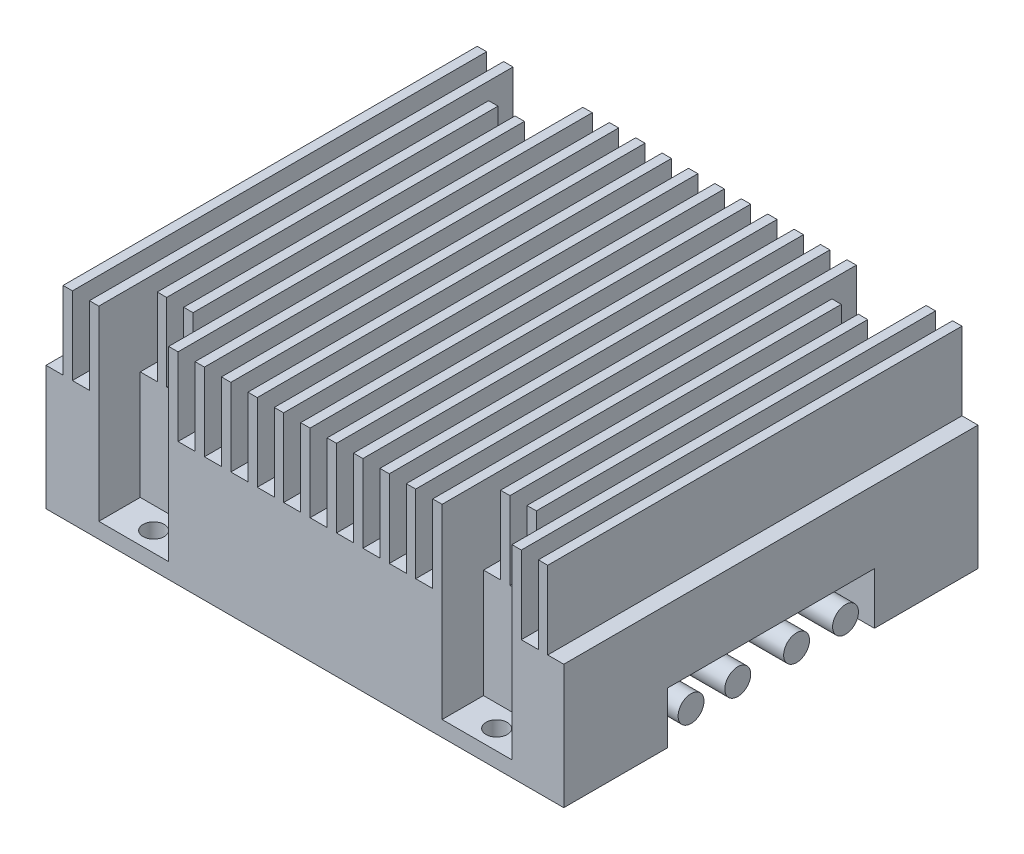
SolidWorks part; units mm, degrees
ref_plane "前视基准面" through (0, 0, 0) normal (0, 0, 1) x (1, 0, 0)
ref_plane "上视基准面" through (0, 0, 0) normal (0, 1, 0) x (1, 0, 0)
ref_plane "右视基准面" through (0, 0, 0) normal (1, 0, 0) x (0, 0, -1)
sketch "草图1" plane through (0, 0, 0) normal (0, 1, 0) x (1, 0, 0)
  line L1 (-50, 40) -> (50, 40)
  line L2 (-50, 40) -> (-50, -40)
  line L3 (-50, -40) -> (50, -40)
  line L4 (50, 40) -> (50, -40)
  line L5 (-50, 40) -> (50, -40) construction
  line L6 (-50, -40) -> (50, 40) construction
  point P0 (0, 0)
  dimension "D1" = 100
  dimension "D2" = 80
extrude "凸台-拉伸1" add sketch "草图1" along normal blind 39
sketch "草图2" plane through (0, 39, 0) normal (0, 1, 0) x (1, 0, 0)
  line L0 (-50, -40) -> (50, -40) construction
  line L1 (-50, 40) -> (-46.7121, 40)
  line L2 (-50, 40) -> (-50, -40)
  line L3 (-50, -40) -> (-46.7121, -40)
  line L4 (-46.7121, 40) -> (-46.7121, -40)
  line L5 (-44.9, 40) -> (-44.9, -40)
  line L6 (-44.9, 40) -> (-41.6121, 40)
  line L7 (-41.6121, 40) -> (-41.6121, -40)
  line L8 (-44.9, -40) -> (-41.6121, -40)
  line L9 (-39.8, 40) -> (-39.8, -40)
  line L10 (-39.8, 40) -> (-36.5121, 40)
  line L11 (-36.5121, 40) -> (-36.5121, -40)
  line L12 (-39.8, -40) -> (-36.5121, -40)
  line L13 (-34.7, 40) -> (-34.7, -40)
  line L14 (-34.7, 40) -> (-31.4121, 40)
  line L15 (-31.4121, 40) -> (-31.4121, -40)
  line L16 (-34.7, -40) -> (-31.4121, -40)
  line L17 (-29.6, 40) -> (-29.6, -40)
  line L18 (-29.6, 40) -> (-26.3121, 40)
  line L19 (-26.3121, 40) -> (-26.3121, -40)
  line L20 (-29.6, -40) -> (-26.3121, -40)
  line L21 (-24.5, 40) -> (-24.5, -40)
  line L22 (-24.5, 40) -> (-21.2121, 40)
  line L23 (-21.2121, 40) -> (-21.2121, -40)
  line L24 (-24.5, -40) -> (-21.2121, -40)
  line L25 (-19.4, 40) -> (-19.4, -40)
  line L26 (-19.4, 40) -> (-16.1121, 40)
  line L27 (-16.1121, 40) -> (-16.1121, -40)
  line L28 (-19.4, -40) -> (-16.1121, -40)
  line L29 (-14.3, 40) -> (-14.3, -40)
  line L30 (-14.3, 40) -> (-11.0121, 40)
  line L31 (-11.0121, 40) -> (-11.0121, -40)
  line L32 (-14.3, -40) -> (-11.0121, -40)
  line L33 (-9.2, 40) -> (-9.2, -40)
  line L34 (-9.2, 40) -> (-5.9121, 40)
  line L35 (-5.9121, 40) -> (-5.9121, -40)
  line L36 (-9.2, -40) -> (-5.9121, -40)
  line L37 (-4.1, 40) -> (-4.1, -40)
  line L38 (-4.1, 40) -> (-0.8121, 40)
  line L39 (-0.8121, 40) -> (-0.8121, -40)
  line L40 (-4.1, -40) -> (-0.8121, -40)
  line L41 (1, 40) -> (1, -40)
  line L42 (1, 40) -> (4.2879, 40)
  line L43 (4.2879, 40) -> (4.2879, -40)
  line L44 (1, -40) -> (4.2879, -40)
  line L45 (6.1, 40) -> (6.1, -40)
  line L46 (6.1, 40) -> (9.3879, 40)
  line L47 (9.3879, 40) -> (9.3879, -40)
  line L48 (6.1, -40) -> (9.3879, -40)
  line L49 (11.2, 40) -> (11.2, -40)
  line L50 (11.2, 40) -> (14.4879, 40)
  line L51 (14.4879, 40) -> (14.4879, -40)
  line L52 (11.2, -40) -> (14.4879, -40)
  line L53 (16.3, 40) -> (16.3, -40)
  line L54 (16.3, 40) -> (19.5879, 40)
  line L55 (19.5879, 40) -> (19.5879, -40)
  line L56 (16.3, -40) -> (19.5879, -40)
  line L57 (21.4, 40) -> (21.4, -40)
  line L58 (21.4, 40) -> (24.6879, 40)
  line L59 (24.6879, 40) -> (24.6879, -40)
  line L60 (21.4, -40) -> (24.6879, -40)
  line L61 (26.5, 40) -> (26.5, -40)
  line L62 (26.5, 40) -> (29.7879, 40)
  line L63 (29.7879, 40) -> (29.7879, -40)
  line L64 (26.5, -40) -> (29.7879, -40)
  line L65 (31.6, 40) -> (31.6, -40)
  line L66 (31.6, 40) -> (34.8879, 40)
  line L67 (34.8879, 40) -> (34.8879, -40)
  line L68 (31.6, -40) -> (34.8879, -40)
  line L69 (36.7, 40) -> (36.7, -40)
  line L70 (36.7, 40) -> (39.9879, 40)
  line L71 (39.9879, 40) -> (39.9879, -40)
  line L72 (36.7, -40) -> (39.9879, -40)
  line L73 (41.8, 40) -> (41.8, -40)
  line L74 (41.8, 40) -> (45.0879, 40)
  line L75 (45.0879, 40) -> (45.0879, -40)
  line L76 (41.8, -40) -> (45.0879, -40)
  line L77 (46.9, 40) -> (46.9, -40)
  line L78 (46.9, 40) -> (50.1879, 40)
  line L79 (50.1879, 40) -> (50.1879, -40)
  line L80 (46.9, -40) -> (50.1879, -40)
  dimension "D1" = 20
extrude "切除-拉伸1" cut sketch "草图2" against normal blind 15
sketch "草图3" plane through (0, 24, 0) normal (0, 1, 0) x (1, 0, 0)
  line L0 (-26.3121, -40) -> (-26.3121, 40) construction
  line L1 (-39.8, 40) -> (-26.3121, 40)
  line L2 (-39.8, 40) -> (-39.8, 32)
  line L3 (-39.8, 32) -> (-26.3121, 32)
  line L4 (-26.3121, 40) -> (-26.3121, 32)
  dimension "D1" = 8
extrude "切除-拉伸2" cut sketch "草图3" against normal blind 21
extrude "切除-拉伸3" cut sketch "草图3<2>" along normal blind 15
sketch "草图3<2>" plane through (0, 24, 0) normal (0, 1, 0) x (1, 0, 0) same geometry as "草图3"
sketch "草图4" plane through (0, 24, 0) normal (0, 1, 0) x (1, 0, 0)
  line L0 (26.5, 40) -> (26.5, -40) construction
  line L1 (39.9879, 40) -> (26.5, 40)
  line L2 (39.9879, 40) -> (39.9879, 32)
  line L3 (39.9879, 32) -> (26.5, 32)
  line L4 (26.5, 40) -> (26.5, 32)
  dimension "D1" = 8
extrude "切除-拉伸4" cut sketch "草图4" against normal blind 21
extrude "切除-拉伸5" cut sketch "草图4<3>" along normal blind 15
sketch "草图4<3>" plane through (0, 24, 0) normal (0, 1, 0) x (1, 0, 0) same geometry as "草图4"
sketch "草图5" plane through (0, 24, 0) normal (0, 1, 0) x (1, 0, 0)
  line L0 (-26.3121, -40) -> (-26.3121, 32) construction
  line L1 (-39.8, -40) -> (-26.3121, -40)
  line L2 (-39.8, -40) -> (-39.8, -32)
  line L3 (-39.8, -32) -> (-26.3121, -32)
  line L4 (-26.3121, -40) -> (-26.3121, -32)
  dimension "D1" = 8
extrude "切除-拉伸6" cut sketch "草图5" against normal blind 21
extrude "切除-拉伸7" cut sketch "草图5<2>" along normal blind 15
sketch "草图5<2>" plane through (0, 24, 0) normal (0, 1, 0) x (1, 0, 0) same geometry as "草图5"
sketch "草图6" plane through (0, 39, 0) normal (0, 1, 0) x (1, 0, 0)
  line L0 (26.5, 40) -> (26.5, -40) construction
  line L1 (39.9879, -40) -> (26.5, -40)
  line L2 (39.9879, -40) -> (39.9879, -32)
  line L3 (39.9879, -32) -> (26.5, -32)
  line L4 (26.5, -40) -> (26.5, -32)
  dimension "D1" = 8
extrude "切除-拉伸8" cut sketch "草图6" against normal blind 21
extrude "切除-拉伸9" cut sketch "草图6<2>" against normal blind 36
sketch "草图6<2>" plane through (0, 39, 0) normal (0, 1, 0) x (1, 0, 0) same geometry as "草图6"
sketch "草图7" plane through (0, 3, 0) normal (0, 1, 0) x (1, 0, 0)
  circle A0 centre (-33.3959, 36.0216) radius 2.05
  dimension "D1" = 4.1
extrude "切除-拉伸10" cut sketch "草图7" against normal blind 3
sketch "草图8" plane through (0, 3, 0) normal (0, 1, 0) x (1, 0, 0)
  circle A0 centre (33.3128, 35.9407) radius 2.05
  dimension "D1" = 4.1
extrude "切除-拉伸11" cut sketch "草图8" against normal blind 3
sketch "草图9" plane through (0, 3, 0) normal (0, 1, 0) x (1, 0, 0)
  circle A0 centre (-32.9708, -36.238) radius 2.05
  dimension "D1" = 4.1
extrude "切除-拉伸12" cut sketch "草图9" against normal blind 3
sketch "草图10" plane through (0, 3, 0) normal (0, 1, 0) x (1, 0, 0)
  circle A0 centre (33.2521, -36.225) radius 2.05
  dimension "D1" = 4.1
extrude "切除-拉伸13" cut sketch "草图10" against normal blind 3
sketch "草图11" plane through (50, 0, 0) normal (1, 0, 0) x (0, 0, -1)
  line L1 (-20, 10) -> (20, 10)
  line L2 (-20, 10) -> (-20, -10)
  line L3 (-20, -10) -> (20, -10)
  line L4 (20, 10) -> (20, -10)
  line L5 (-20, 10) -> (20, -10) construction
  line L6 (-20, -10) -> (20, 10) construction
  point P0 (0, 0)
  dimension "D1" = 40
  dimension "D2" = 20
extrude "切除-拉伸14" cut sketch "草图11" against normal blind 10
sketch "草图12" plane through (40, 0, 0) normal (1, 0, 0) x (0, 0, -1)
  circle A0 centre (-15.4221, 4.287) radius 2.5
  circle A1 centre (-6.3965, 4.287) radius 2.5
  circle A2 centre (4.9622, 4.287) radius 2.5
  circle A3 centre (14.4175, 4.287) radius 2.5
  dimension "D1" = 5
  dimension "D2" = 5
  dimension "D3" = 5
  dimension "D4" = 5
extrude "凸台-拉伸2" add sketch "草图12" along normal blind 10
